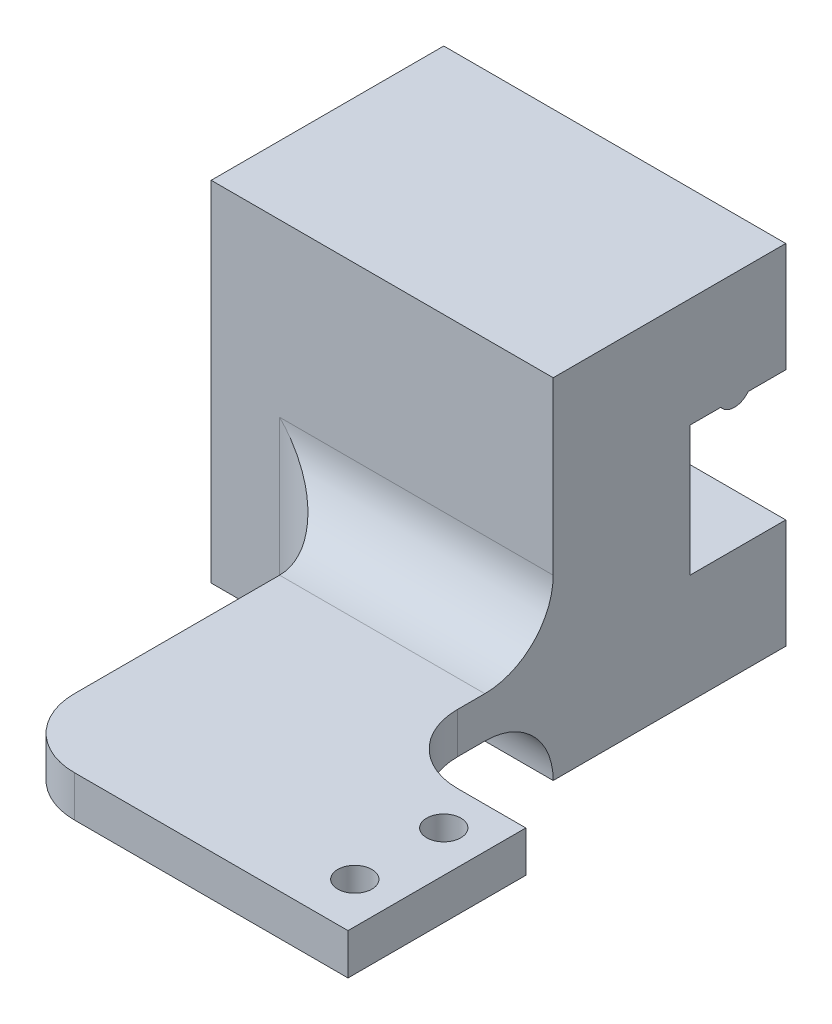
SolidWorks part; units mm, degrees
ref_plane "Front Plane" through (0, 0, 0) normal (0, 0, 1) x (1, 0, 0)
ref_plane "Top Plane" through (0, 0, 0) normal (0, 1, 0) x (1, 0, 0)
ref_plane "Right Plane" through (0, 0, 0) normal (1, 0, 0) x (0, 0, -1)
sketch "Sketch1" plane through (0, 0, 0) normal (0, 0, 1) x (1, 0, 0)
  line L0 (0, 0) -> (-18, 0)
  line L1 (-18, 0) -> (-18, -8)
  line L2 (-18, -8) -> (0, -8)
  line L3 (0, -8) -> (0, -17.5)
  line L4 (0, -17.5) -> (-18, -17.5)
  line L5 (-18, -17.5) -> (-18, -25.5)
  line L6 (-18, -25.5) -> (10, -25.5)
  line L7 (10, -25.5) -> (10, 0)
  line L8 (10, 0) -> (0, 0)
  arc A0 (-4.25, -8) -> (-2.25, -8) centre (-3.25, -7.25) ccw
  point P13 (-3.25, -8.5)
  dimension "D7" = 3.25
  dimension "D1" = 18
  dimension "D2" = 9.5
  dimension "D3" = 8
  dimension "D4" = 8
  dimension "D5" = 10
  dimension "D6" = 9
  dimension "D8" = 1
  dimension "D9" = 28
extrude "Boss-Extrude1" add sketch "Sketch1" along normal blind 50 contours L2 A0 | L7 L8 L0 L1 L2 L3 L4 L5 L6 region at (5, -0.3787, 0) region at (-3.25, -8.2039, 0)
sketch "Sketch2" plane through (0, 0, 0) normal (1, 0, 0) x (0, 0, -1)
  line L9 (0, 0) -> (0, -50) construction
  line L10 (7, -8) -> (0, -8)
  line L11 (0, -17.5) -> (7, -17.5)
  line L12 (0, -8) -> (0, -17.5)
  line L13 (7, -17.5) -> (7, -25.5)
  line L14 (7, -25.5) -> (-10, -25.5)
  line L15 (-10, -25.5) -> (-10, 0)
  line L16 (-10, 0) -> (0, 0)
  line L17 (0, 0) -> (7, 0)
  line L18 (7, 0) -> (7, -8)
  arc A1 (4.25, -8) -> (2.25, -8) centre (3.25, -7.25) cw
  dimension "D13" = 1.25
  dimension "D2" = 17
  dimension "D3" = 3.25
  dimension "D4" = 25.5
  dimension "D5" = 1
  dimension "D6" = 9.5
  dimension "D7" = 8
  dimension "D8" = 8
  dimension "D9" = 10
  dimension "D10" = 10
  dimension "D11" = 50
  dimension "D12" = 7
  dimension "D16" = 0.75
extrude "Boss-Extrude2" add sketch "Sketch2" along normal blind 50 contours L17 L9 L10 L18 | L9 L16 L15 L14 L12 | L11 L9 L14 L13 | A1 L10 region at (0, -4, -3.5) region at (0, -12.75, 5) region at (0, -21.5, -3.5) region at (0, -8.2039, -3.25)
extrude "Boss-Extrude3" add sketch "Sketch2<3>" against normal up to surface (18 mm away) contours L17 L9 L10 L18 | L11 L9 L14 L13 region at (0, -4, -3.5) region at (0, -21.5, -3.5) up to face at (-18, -4, 25)
sketch "Sketch2<3>" plane through (0, 0, 0) normal (1, 0, 0) x (0, 0, -1) same geometry as "Sketch2"
sketch "Sketch3" plane through (50, 0, 0) normal (1, 0, 0) x (0, 0, -1)
  line L0 (0, -17.5) -> (32.5, -17.5)
  line L1 (0, -25.5) -> (0, -88.5)
  line L2 (7, -25.5) -> (-10, -25.5) construction
  line L3 (0, -17.5) -> (0, -25.5)
  line L4 (32.5, -17.5) -> (32.5, -88.5)
  line L5 (32.5, -88.5) -> (0, -88.5)
  line L6 (0, -17.5) -> (-10, -17.5)
  line L7 (-10, -25.5) -> (-10, 0) construction
  line L8 (-10, -17.5) -> (-10, -88.5)
  line L9 (-10, -88.5) -> (0, -88.5)
  line M3 (-10, 0) -> (-10, -25.5)
  line M4 (-10, -25.5) -> (7, -25.5)
  line M5 (7, -25.5) -> (7, -17.5)
  line M6 (7, -17.5) -> (0, -17.5)
  dimension "D1" = 32.5
  dimension "D2" = 63
ref_plane "Wall" through (-32, 0, 0) normal (-1, 0, 0) x (0, 0, 1)
extrude "Boss-Extrude4" add sketch "Sketch3" against normal up to surface (82 mm away) contours L5 L4 L0 L1 M5 M4 | L8 L9 L1 M4 | L3 M6 M4 M5 | L3 L6 M3 M4 region at (50, -21.5, -3.5) region at (50, -21.5, 5) region at (50, -53.7835, -16.5671) region at (50, -57, 5) up to plane "Wall"
fillet "Fillet1" radius 5 3 edges at (-32, -53, -32.5) (-32, -17.5, -11.25) (9, -17.5, -32.5)
sketch "Sketch4" plane through (0, -88.5, 0) normal (0, -1, 0) x (1, 0, 0)
  line L0 (50, 10) -> (50, -15.5)
  line L1 (50, -32.5) -> (50, 10) construction
  line L2 (50, -15.5) -> (1, -15.5)
  line L3 (1, -15.5) -> (1, 10)
  line L4 (-18, 10) -> (10, 10) construction
  line L5 (1, 10) -> (50, 10)
  line L6 (-32, -27.5) -> (-32, 10) construction
  line L7 (-27, -32.5) -> (50, -32.5) construction
  dimension "D1" = 33
  dimension "D2" = 17
extrude "Cut-Extrude1" cut sketch "Sketch4" against normal up to surface (63 mm away) up to face at (-4, -25.5, 30)
sketch "Sketch5" plane through (50, 0, 0) normal (1, 0, 0) x (0, 0, -1)
  line L0 (-10, -35.5) -> (15.5, -35.5)
  line L1 (-10, -25.5) -> (-10, -88.5) construction
  line L2 (15.5, -25.5) -> (15.5, -88.5) construction
  line L3 (15.5, -35.5) -> (15.5, -76.5)
  line L4 (15.5, -76.5) -> (-10, -76.5)
  line L5 (-10, -76.5) -> (-10, -35.5)
  line L6 (0, -17.5) -> (27.5, -17.5) construction
  line L7 (-10, -35.5) -> (-10, -25.5)
  line L8 (-10, -25.5) -> (15.5, -25.5)
  line L9 (15.5, -25.5) -> (15.5, -35.5)
  line L10 (-10, -76.5) -> (-10, -88.5)
  line L11 (-10, -88.5) -> (15.5, -88.5)
  line L12 (15.5, -88.5) -> (15.5, -76.5)
  line M3 (-10, -25.5) -> (15.5, -25.5)
  line M4 (15.5, -25.5) -> (15.5, -88.5)
  dimension "D1" = 18
  dimension "D2" = 41
extrude "Boss-Extrude5" add sketch "Sketch5" against normal up to surface (49 mm away) contours L7 L0 M4 M3 | L10 L11 L4 M4 region at (50, -30.5, -2.75) region at (50, -82.5, -2.75) up to face at (1, -57, -2.75)
sketch "Sketch7" plane through (0, 0, 10) normal (0, 0, 1) x (1, 0, 0)
  line L0 (1, -35.5) -> (27, -35.5)
  line L1 (1, -35.5) -> (50, -35.5) construction
  line L2 (27, -35.5) -> (27, -25.5)
  line L3 (27, -25.5) -> (50, -25.5)
  line L4 (50, -35.5) -> (50, 0) construction
  line L5 (50, -25.5) -> (50, -88.5)
  line L6 (50, -88.5) -> (27, -88.5)
  line L7 (-32, -88.5) -> (50, -88.5) construction
  line L8 (27, -88.5) -> (27, -76.5)
  line L9 (1, -76.5) -> (50, -76.5) construction
  line L10 (27, -76.5) -> (1, -76.5)
  line L11 (1, -76.5) -> (1, -35.5)
  dimension "D1" = 26
  dimension "D2" = 26
  dimension "D3" = 10
extrude "Cut-Extrude2" cut sketch "Sketch7" against normal up to surface (25.5 mm away) up to face at (25.5, -56, -15.5)
sketch "Sketch6" plane through (27, 0, 0) normal (1, 0, 0) x (0, 0, -1)
  line L0 (-10, -35.5) -> (-10, -76.5)
  line L2 (-5, -57) -> (15.5, -57)
  line L3 (15.5, -25.5) -> (15.5, -88.5) construction
  line L4 (5.25, -57) -> (5.25, -88.5)
  line L5 (32.5, -88.5) -> (15.5, -88.5) construction
  line L6 (0.25, -81.5) -> (10.25, -81.5)
  circle A0 centre (0.25, -81.5) radius 1.75
  circle A1 centre (10.25, -81.5) radius 1.75
  circle A2 centre (0.25, -81.5) radius 0.75
  circle A3 centre (10.25, -81.5) radius 0.75
  circle A4 centre (10.25, -32.5) radius 0.75
  circle A5 centre (10.25, -32.5) radius 1.75
  circle A6 centre (0.25, -32.5) radius 0.75
  circle A7 centre (0.25, -32.5) radius 1.75
  point P16 (5.25, -81.5)
  dimension "D4" = 3.5
  dimension "D5" = 1.5
  dimension "D6" = 1.5
  dimension "D7" = 3.5
  dimension "D1" = 24.5
  dimension "D2" = 24.5
  dimension "D3" = 10
  dimension "D8" = 20.5
extrude "Cut-Extrude3" cut sketch "Sketch6" against normal blind 5 contours A7 A6 | A6 | A5 A4 | A4 | A2 A0 | A2 | A3 A1 | A3 region at (27, -81.5, 1.4505) region at (27, -80.7712, -10.25) region at (27, -79.7995, -10.25) region at (27, -81.5, 0.4788) region at (27, -32.5, -10.25) region at (27, -32.5, -8.5495) region at (27, -32.5, -0.25) region at (27, -32.5, 1.4505)
extrude "Cut-Extrude4" cut sketch "Sketch6<6>" against normal blind 15 contours A6 | A4 | A2 | A3 region at (27, -81.5, 0.4788) region at (27, -32.5, -10.25) region at (27, -32.5, -0.25)
sketch "Sketch6<6>" plane through (27, 0, 0) normal (1, 0, 0) x (0, 0, -1) same geometry as "Sketch6"
sketch "Sketch8" plane through (0, 0, -7) normal (0, 0, -1) x (-1, 0, 0)
  line L0 (0, -8) -> (18, -8)
  line L1 (18, -8) -> (18, -17.5)
  line L2 (-50, -17.5) -> (27, -17.5) construction
  line L3 (18, -17.5) -> (0, -17.5)
  line L4 (0, -17.5) -> (0, -8)
extrude "Cut-Extrude5" cut sketch "Sketch8" against normal blind 40
sketch "Sketch9" plane through (10, 0, 0) normal (1, 0, 0) x (0, 0, -1)
  line L0 (-10, 0) -> (-10, -25.5)
  line L1 (-10, -25.5) -> (-50, -25.5)
  line L2 (-50, -25.5) -> (-50, 0)
  line L3 (-50, 0) -> (-10, 0)
extrude "Cut-Extrude6" cut sketch "Sketch9" against normal through all
sketch "Sketch10" plane through (0, 0, 10) normal (0, 0, 1) x (1, 0, 0)
  line L0 (0, 0) -> (-32, 0)
  line L2 (-32, 5.225) -> (-32, -5.225) construction
  line L3 (-32, 0) -> (-32, -88.5)
  line L4 (-32, -88.5) -> (0, -88.5)
  line L5 (-32, -88.5) -> (27, -88.5) construction
  line L6 (0, -88.5) -> (0, 0)
extrude "Cut-Extrude7" cut sketch "Sketch10" against normal through all
sketch "Sketch11" plane through (0, 0, -15.5) normal (0, 0, 1) x (1, 0, 0)
  line L0 (50, -25.5) -> (0, -25.5)
  line L1 (0, -88.5) -> (0, 0) construction
  line L2 (0, -25.5) -> (0, -88.5)
  line L3 (0, -88.5) -> (50, -88.5)
  line L4 (50, -88.5) -> (50, -25.5)
extrude "Cut-Extrude8" cut sketch "Sketch11" along normal through all
sketch "Sketch12" plane through (0, 0, 0) normal (-1, 0, 0) x (0, 0, 1)
  line L0 (-15.5, -17.5) -> (-15.5, -42.5)
  line L1 (-27.5, -17.5) -> (0, -17.5) construction
  line L2 (-15.5, -25.5) -> (-15.5, -88.5) construction
  line L3 (10, -25.5) -> (-15.5, -25.5)
  line L4 (-15.5, -25.5) -> (-15.5, -60.5)
  line L5 (-15.5, -60.5) -> (10, -60.5)
  line L6 (10, -60.5) -> (10, -25.5)
  circle A0 centre (-5.5, -42.5) radius 10
  line M4 (-15.5, -25.5) -> (10, -25.5)
  line M16 (-15.5, -88.5) -> (-15.5, -25.5)
  dimension "D2" = 20
  dimension "D1" = 25
  dimension "D3" = 35
extrude "Boss-Extrude7" add sketch "Sketch12" against normal blind 10 contours A0 L5 L6 M16 M4 | A0 region at (0, -42.5, -5.5) region at (0, -25.933, -2.75)
extrude "Cut-Extrude9" cut sketch "Sketch12<3>" against normal through all contours A0 region at (0, -42.5, -5.5)
sketch "Sketch12<3>" plane through (0, 0, 0) normal (-1, 0, 0) x (0, 0, 1) same geometry as "Sketch12"
sketch "Sketch13" plane through (50, 0, 0) normal (1, 0, 0) x (0, 0, -1)
  line L0 (-10, 0) -> (-10, -88.5)
  line L1 (-10, -88.5) -> (32.5, -88.5)
  line L2 (32.5, -88.5) -> (32.5, 0)
  line L3 (32.5, 0) -> (-10, 0)
extrude "Cut-Extrude10" cut sketch "Sketch13" against normal blind 25
sketch "Sketch14" plane through (0, 0, -15.5) normal (0, 0, 1) x (1, 0, 0)
  line L0 (0, -60.5) -> (25, -60.5)
  line L1 (25, -25.5) -> (25, -88.5) construction
  line L2 (25, -60.5) -> (25, -88.5)
  line L3 (25, -88.5) -> (0, -88.5)
  line L4 (0, -88.5) -> (0, -60.5)
extrude "Cut-Extrude11" cut sketch "Sketch14" against normal through all
sketch "Sketch15" plane through (0, 0, -7) normal (0, 0, -1) x (-1, 0, 0)
  line L0 (-25, 0) -> (0, 0)
  line L1 (0, 0) -> (0, -60.5)
  line L2 (0, -60.5) -> (-25, -60.5)
  line L3 (-25, -60.5) -> (-25, 0)
extrude "Cut-Extrude12" cut sketch "Sketch15" along normal through all
sketch "Sketch16" plane through (0, 0, -7) normal (0, 0, -1) x (-1, 0, 0)
  line L0 (-10, -25.5) -> (0, -25.5)
  line L1 (0, -32.6131) -> (0, -17.5) construction
  line L2 (0, -25.5) -> (0, -60.5)
  line L3 (0, -60.5) -> (-10, -60.5)
  line L4 (-10, -60.5) -> (-10, -25.5)
extrude "Cut-Extrude13" cut sketch "Sketch16" against normal through all
sketch "Sketch17" plane through (0, -17.5, 0) normal (0, 1, 0) x (1, 0, 0)
  line L0 (25, 0) -> (10, 0)
  line L1 (10, 0) -> (10, -35)
  line L2 (10, -35) -> (25, -35)
  line L3 (25, -35) -> (25, 0)
  dimension "D1" = 35
  dimension "D2" = 15
extrude "Boss-Extrude8" add sketch "Sketch17" against normal blind 3
sketch "Sketch18" plane through (25, 0, 0) normal (1, 0, 0) x (0, 0, -1)
  line L0 (-35, -17.5) -> (-35, -20.5)
  line L1 (-35, -20.5) -> (0, -20.5)
  line L2 (0, -20.5) -> (0, -17.5)
  line L3 (0, -17.5) -> (-35, -17.5)
  line M9 (-10, -17.5) -> (-35, -17.5)
  line M10 (-35, -17.5) -> (-35, -20.5)
  line M11 (-35, -20.5) -> (-10, -20.5)
extrude "Boss-Extrude9" add sketch "Sketch18" along normal blind 10 contours L2 L3 L1 M9 M10 M11 region at (25, -19, 17.5)
sketch "Sketch19" plane through (0, -20.5, 0) normal (0, -1, 0) x (1, 0, 0)
  line L0 (35, 0) -> (25, 0) construction
  line L2 (35, 22) -> (35, 0)
  line L3 (35, 0) -> (25, 0)
  line L4 (25, 0) -> (25, 22)
  line L5 (25, 22) -> (35, 22)
  line L6 (35, 35) -> (35, 0) construction
  line L7 (35, 0) -> (25, 0) construction
  circle A0 centre (32, 31.5) radius 1.25
  circle A1 centre (32, 25) radius 1.25
  point P6 (35, 0)
  line M4 (25, 10) -> (25, 0)
  line M5 (25, 0) -> (35, 0)
  line M13 (35, 0) -> (35, 35)
  dimension "D1" = 2.5
  dimension "D2" = 2.5
  dimension "D3" = 25
  dimension "D4" = 6.5
  dimension "D5" = 3
  dimension "D6" = 3
  dimension "D7" = 22
extrude "Cut-Extrude14" cut sketch "Sketch19" against normal through all contours L5 L4 M4 M5 M13 | A1 | A0 region at (30, -20.5, 11) region at (32, -20.5, 31.5) region at (32, -20.5, 25)
fillet "Fillet4" radius 5 5 edges at (25, -19, 22) (10, -19, 35) (10, -19, 10) (17.5, -20.5, 10) (17.5, -17.5, 10)
